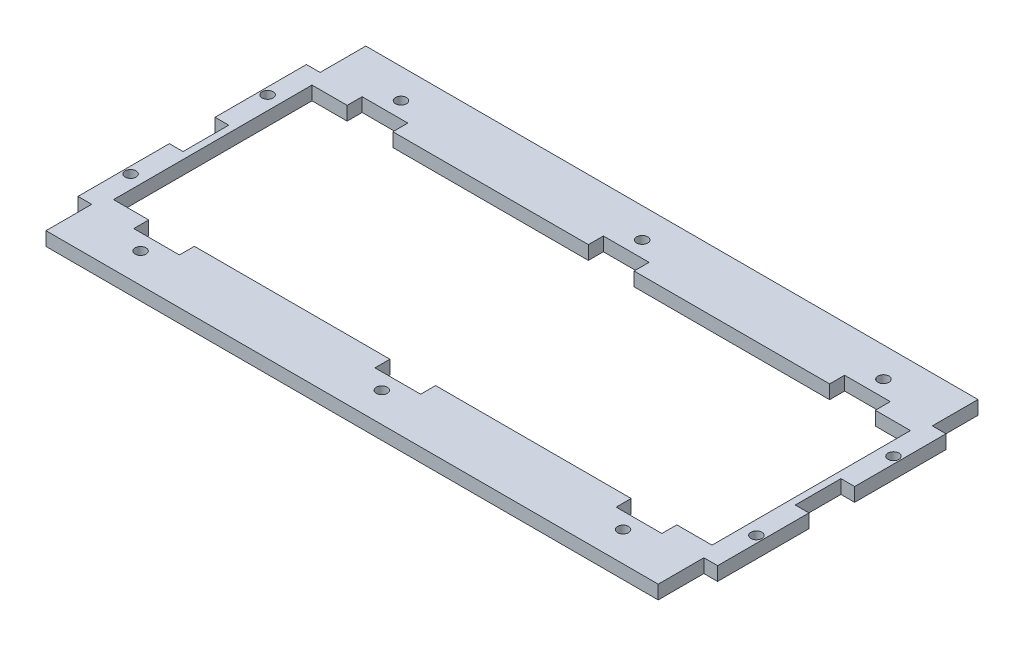
SolidWorks part; units mm, degrees
material "Acrylic (Medium-high impact)"
ref_plane "Front" through (0, 0, 0) normal (0, 0, 1) x (1, 0, 0)
ref_plane "Top" through (0, 0, 0) normal (0, 1, 0) x (1, 0, 0)
ref_plane "Right" through (0, 0, 0) normal (1, 0, 0) x (0, 0, -1)
sketch "Sketch1" plane through (0, 0, 0) normal (0, 1, 0) x (1, 0, 0)
  line L0 (-85.09, 0) -> (85.09, 0) construction
  line L1 (-85.09, -44.45) -> (85.09, -44.45)
  line L3 (-85.09, 44.45) -> (85.09, 44.45)
  line L4 (88.9, -31.75) -> (88.9, -6.35)
  line L5 (85.09, -44.45) -> (85.09, -31.75)
  line L6 (85.09, -31.75) -> (88.9, -31.75)
  line L7 (0, 44.45) -> (0, -44.45) construction
  line L8 (88.9, -6.35) -> (85.09, -6.35)
  line L9 (85.09, -6.35) -> (85.09, 6.35)
  line L10 (85.09, 6.35) -> (88.9, 6.35)
  line L11 (88.9, 31.75) -> (85.09, 31.75)
  line L12 (85.09, 31.75) -> (85.09, 44.45)
  line L13 (88.9, 6.35) -> (88.9, 31.75)
  line L14 (-88.9, 6.35) -> (-88.9, 31.75)
  line L15 (-85.09, 31.75) -> (-85.09, 44.45)
  line L16 (-88.9, 31.75) -> (-85.09, 31.75)
  line L17 (-85.09, 6.35) -> (-88.9, 6.35)
  line L18 (-85.09, -6.35) -> (-85.09, 6.35)
  line L19 (-88.9, -6.35) -> (-85.09, -6.35)
  line L20 (-85.09, -31.75) -> (-88.9, -31.75)
  line L21 (-85.09, -44.45) -> (-85.09, -31.75)
  line L22 (-88.9, -31.75) -> (-88.9, -6.35)
  line L24 (86.995, 31.75) -> (86.995, 6.35) construction
  line L32 (-83.185, -27.5844) -> (-73.406, -27.5844)
  line L33 (-73.406, -27.5844) -> (-73.406, -31.75)
  line L34 (-73.406, -31.75) -> (-60.706, -31.75)
  line L35 (-60.706, -31.75) -> (-60.706, -27.5844)
  line L36 (-60.706, -27.5844) -> (-6.35, -27.5844)
  line L37 (-6.35, -27.5844) -> (-6.35, -31.75)
  line L38 (-6.35, -31.75) -> (6.35, -31.75)
  line L39 (6.35, -31.75) -> (6.35, -27.5844)
  line L40 (6.35, -27.5844) -> (60.706, -27.5844)
  line L41 (60.706, -27.5844) -> (60.706, -31.75)
  line L42 (60.706, -31.75) -> (73.406, -31.75)
  line L43 (73.406, -31.75) -> (73.406, -27.5844)
  line L44 (73.406, -27.5844) -> (83.185, -27.5844)
  line L45 (83.185, -27.5844) -> (83.185, 27.5844)
  line L46 (83.185, 27.5844) -> (73.406, 27.5844)
  line L47 (73.406, 27.5844) -> (73.406, 31.75)
  line L48 (73.406, 31.75) -> (60.706, 31.75)
  line L49 (60.706, 31.75) -> (60.706, 27.5844)
  line L50 (60.706, 27.5844) -> (6.35, 27.5844)
  line L51 (6.35, 27.5844) -> (6.35, 31.75)
  line L52 (6.35, 31.75) -> (-6.35, 31.75)
  line L53 (-6.35, 31.75) -> (-6.35, 27.5844)
  line L54 (-6.35, 27.5844) -> (-60.706, 27.5844)
  line L55 (-60.706, 27.5844) -> (-60.706, 31.75)
  line L56 (-60.706, 31.75) -> (-73.406, 31.75)
  line L57 (-73.406, 31.75) -> (-73.406, 27.5844)
  line L58 (-73.406, 27.5844) -> (-83.185, 27.5844)
  line L59 (-83.185, 27.5844) -> (-83.185, -27.5844)
  line L60 (-67.056, -31.75) -> (-67.056, -44.45) construction
  circle A0 centre (86.995, 19.05) radius 1.524
  circle A1 centre (-86.995, 19.05) radius 1.524
  circle A2 centre (-86.995, -19.05) radius 1.524
  circle A3 centre (86.995, -19.05) radius 1.524
  circle A4 centre (-67.056, -36.195) radius 1.524
  circle A5 centre (0, -36.195) radius 1.524
  circle A6 centre (67.056, -36.195) radius 1.524
  circle A7 centre (67.056, 36.195) radius 1.524
  circle A8 centre (-67.056, 36.195) radius 1.524
  circle A9 centre (0, 36.195) radius 1.524
  point P0 (0, 0)
  point P10 (0, 0)
  point P20 (85.09, 0)
  point P71 (-83.185, 0)
  point P73 (0, 31.75)
  dimension "D5" = 3.048
  dimension "D6" = 55.1688
  dimension "D1" = 177.8
  dimension "D2" = 88.9
  dimension "D3" = 3.81
  dimension "D4" = 25.4
  dimension "D7" = 12.7
  dimension "D8" = 63.5
  dimension "D9" = 166.37
  dimension "D10" = 54.356
  dimension "D12" = 72.39
  dimension "D11" = 3
extrude "Boss-Extrude1" add sketch "Sketch1" along normal blind 3.81
